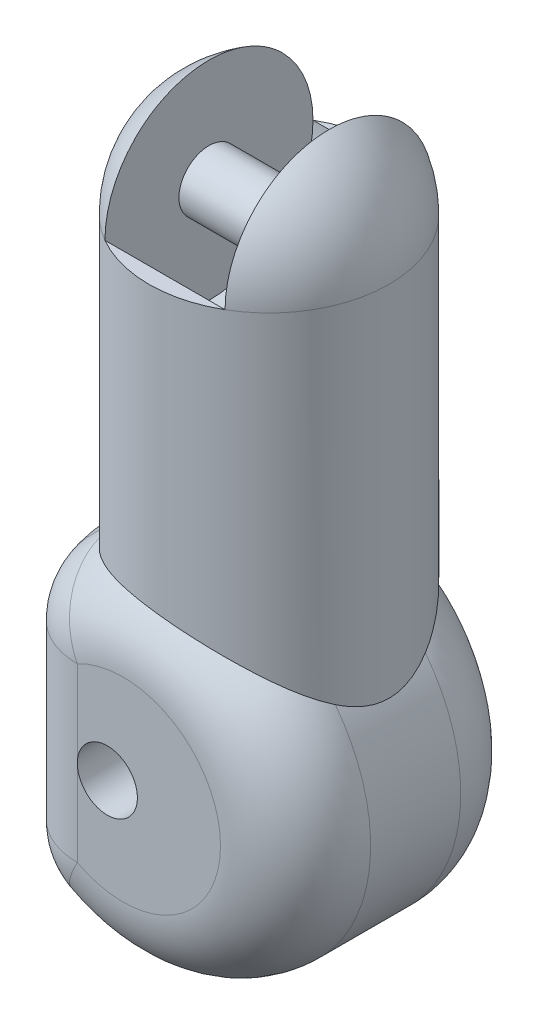
SolidWorks part; units mm, degrees
ref_plane "Front Plane" through (0, 0, 0) normal (0, 0, 1) x (1, 0, 0)
ref_plane "Top Plane" through (0, 0, 0) normal (0, 1, 0) x (1, 0, 0)
ref_plane "Right Plane" through (0, 0, 0) normal (1, 0, 0) x (0, 0, -1)
sketch "Sketch1" plane through (0, 0, 0) normal (0, 1, 0) x (1, 0, 0)
  line L1 (0, -40) -> (57.45, -40)
  line L2 (0, -40) -> (0, 40)
  line L3 (0, 40) -> (57.45, 40)
  line L4 (57.45, -40) -> (57.45, 40)
  point P4 (0, 0)
  dimension "D1" = 57.45
  dimension "D2" = 80
revolve "Revolve2" add sketch "Sketch1" angle 360 about L2
sketch "Sketch2" plane through (0, 0, 0) normal (0, 1, 0) x (1, 0, 0)
  line L2 (-57.45, -40) -> (57.45, -40) construction
  line L3 (-57.45, 40) -> (-27.45, 40)
  line L4 (-57.45, 40) -> (-57.45, -40)
  line L5 (-57.45, -40) -> (-27.45, -40)
  arc A0 (-27.45, 40) -> (-27.45, -40) centre (12.55, 0) ccw
  dimension "D1" = 30
  dimension "D2" = 30
extrude "Cut-Extrude4" cut sketch "Sketch2" against normal through all and the other way through all contours A0 L5 L4 L3
fillet "Fillet1" radius 25 6 edges at (-27.45, 0, -40) (57.45, 0, -40) (-27.45, 0, 40) (57.45, 0, 40) (-43.9345, -37.0171, -3.0828) (-43.9345, 37.0171, 3.0828)
sketch "Sketch4" plane through (0, 0, 40) normal (0, 0, 1) x (1, 0, 0)
  line L0 (-15.2272, 0) -> (-5.2272, 0)
  line L2 (-15.2272, 28.6555) -> (-15.2272, -28.6555) construction
  circle A0 centre (-5.2272, 0) radius 10
  dimension "D1" = 10
extrude "Cut-Extrude5" cut sketch "Sketch4" against normal through all contours A0 region at (-5.2272, -9.7172, 40)
ref_plane "Plane1" through (0, 70, 0) normal (0, 1, 0) x (1, 0, 0)
sketch "Sketch5" plane through (0, 70, 0) normal (0, 1, 0) x (1, 0, 0)
  line L0 (8.6114, 40) -> (8.6114, -40) construction
  line L1 (32.45, 40) -> (-15.2272, 40) construction
  line L2 (-15.2272, -40) -> (32.45, -40) construction
  circle A0 centre (8.6114, 0) radius 40
extrude "Boss-Extrude1" add sketch "Sketch5" along normal blind 120 and the other way up to surface other way up to face at (11.9257, 0, 0)
fillet "Fillet2" radius 40 1 edges at (8.6114, 190, 40)
sketch "Sketch6" plane through (0, 0, 0) normal (0, 0, 1) x (1, 0, 0)
  line L0 (-31.3886, 150) -> (48.6114, 150)
  line L1 (-31.3886, 150) -> (48.6114, 150) construction
  line L3 (-11.3886, 150) -> (28.6114, 150)
  line L4 (-11.3886, 150) -> (-11.3886, 201.0268)
  line L5 (-11.3886, 201.0268) -> (28.6114, 201.0268)
  line L6 (28.6114, 150) -> (28.6114, 201.0268)
  arc A0 (48.6114, 150) -> (-31.3886, 150) centre (8.6114, 150) ccw construction
  point P11 (8.6114, 201.0268)
  point P12 (8.6114, 150)
  dimension "D1" = 40
extrude "Cut-Extrude6" cut sketch "Sketch6" against normal through all and the other way through all contours L0 L6 L5 L4 region at (8.6114, 175.5134, 0)
sketch "Sketch7" plane through (-11.3886, 0, 0) normal (1, 0, 0) x (0, 0, -1)
  line L0 (-34.641, 150) -> (34.641, 150) construction
  circle A0 centre (0, 150) radius 34.641
extrude "Cut-Extrude7" cut sketch "Sketch7" along normal up to surface (40 mm away) up to face at (28.6114, 167.3205, 0)
sketch "Sketch8" plane through (-11.3886, 0, 0) normal (1, 0, 0) x (0, 0, -1)
  circle A0 centre (0, 150) radius 10
extrude "Boss-Extrude2" add sketch "Sketch8" along normal up to surface (40 mm away) up to face at (28.6114, 150, 0)
